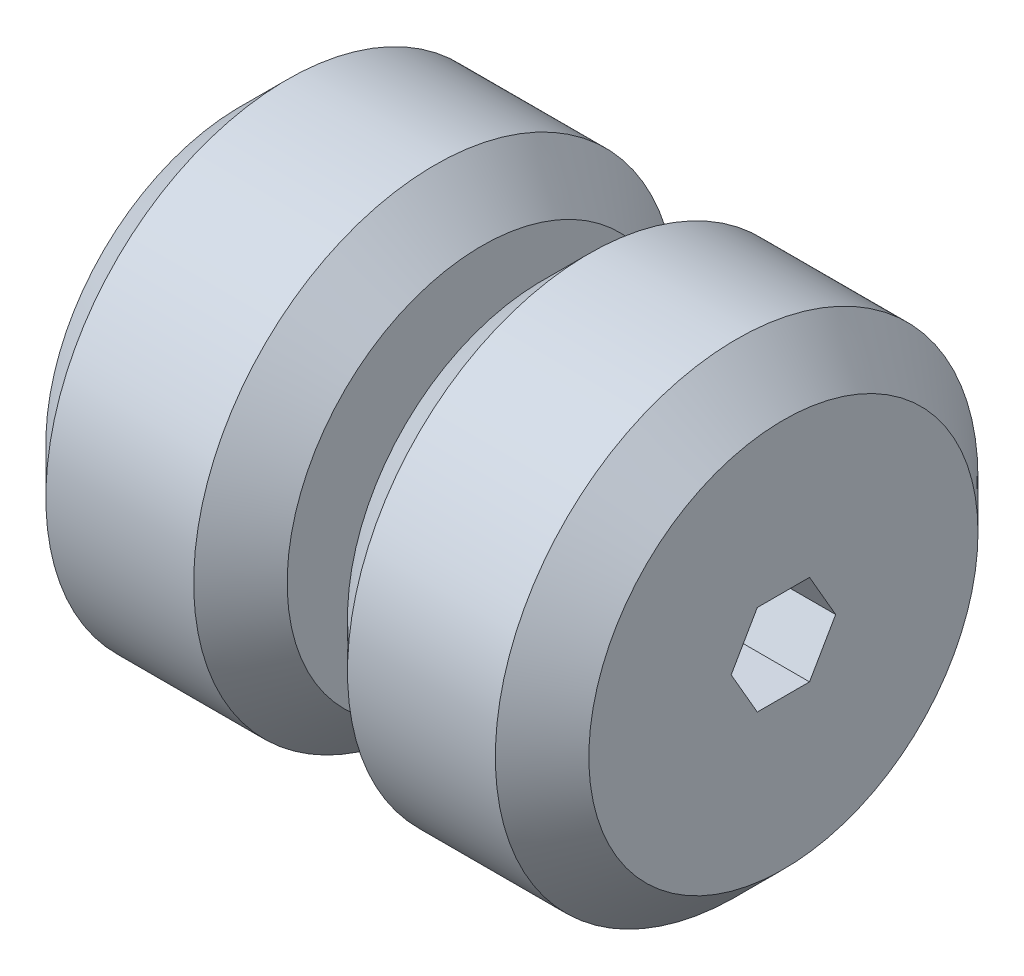
SolidWorks part; units mm, degrees
material "Hexcel AS4C (3000 Filaments)"
ref_plane "Front" through (0, 0, 0) normal (0, 0, 1) x (1, 0, 0)
ref_plane "Top" through (0, 0, 0) normal (0, 1, 0) x (1, 0, 0)
ref_plane "Right" through (0, 0, 0) normal (1, 0, 0) x (0, 0, -1)
sketch "Sketch1" plane through (0, 0, 0) normal (1, 0, 0) x (0, 0, -1)
  circle A0 centre (0, 0) radius 25.4
  dimension "D1" = 50.8
extrude "Boss-Extrude1" add sketch "Sketch1" against normal blind 25.4 from offset 3.175 offset against normal yes
extrude "Boss-Extrude3" add sketch "Sketch1<3>" along normal blind 25.4 from offset 3.175 separate body
sketch "Sketch1<3>" plane through (0, 0, 0) normal (1, 0, 0) x (0, 0, -1) same geometry as "Sketch1"
chamfer "Chamfer1" distance 4.92 angle 45 2 edges at (-3.175, 0, -25.4) (-28.575, 0, -25.4)
chamfer "Chamfer2" distance 4.92 angle 45 2 edges at (28.575, 0, -25.4) (3.175, 0, -25.4)
sketch "Sketch2" plane through (-3.175, 0, 0) normal (1, 0, 0) x (0, 0, -1)
  circle A0 centre (0, 0) radius 9.525
  dimension "D1" = 19.05
extrude "Boss-Extrude4" add sketch "Sketch2" along normal up to surface (6.35 mm away) up to face at (3.175, 0, -20.48)
sketch "Sketch3" plane through (28.575, 0, 0) normal (1, 0, 0) x (0, 0, -1)
  line L1 (2.7496, -4.7625) -> (5.4993, 0)
  line L2 (5.4993, 0) -> (2.7496, 4.7625)
  line L3 (2.7496, 4.7625) -> (-2.7496, 4.7625)
  line L4 (-2.7496, 4.7625) -> (-5.4993, 0)
  line L5 (-5.4993, 0) -> (-2.7496, -4.7625)
  line L6 (-2.7496, -4.7625) -> (2.7496, -4.7625)
  circle A0 centre (0, 0) radius 4.7625 construction
  dimension "D1" = 9.525
extrude "Cut-Extrude1" cut sketch "Sketch3" against normal through all
